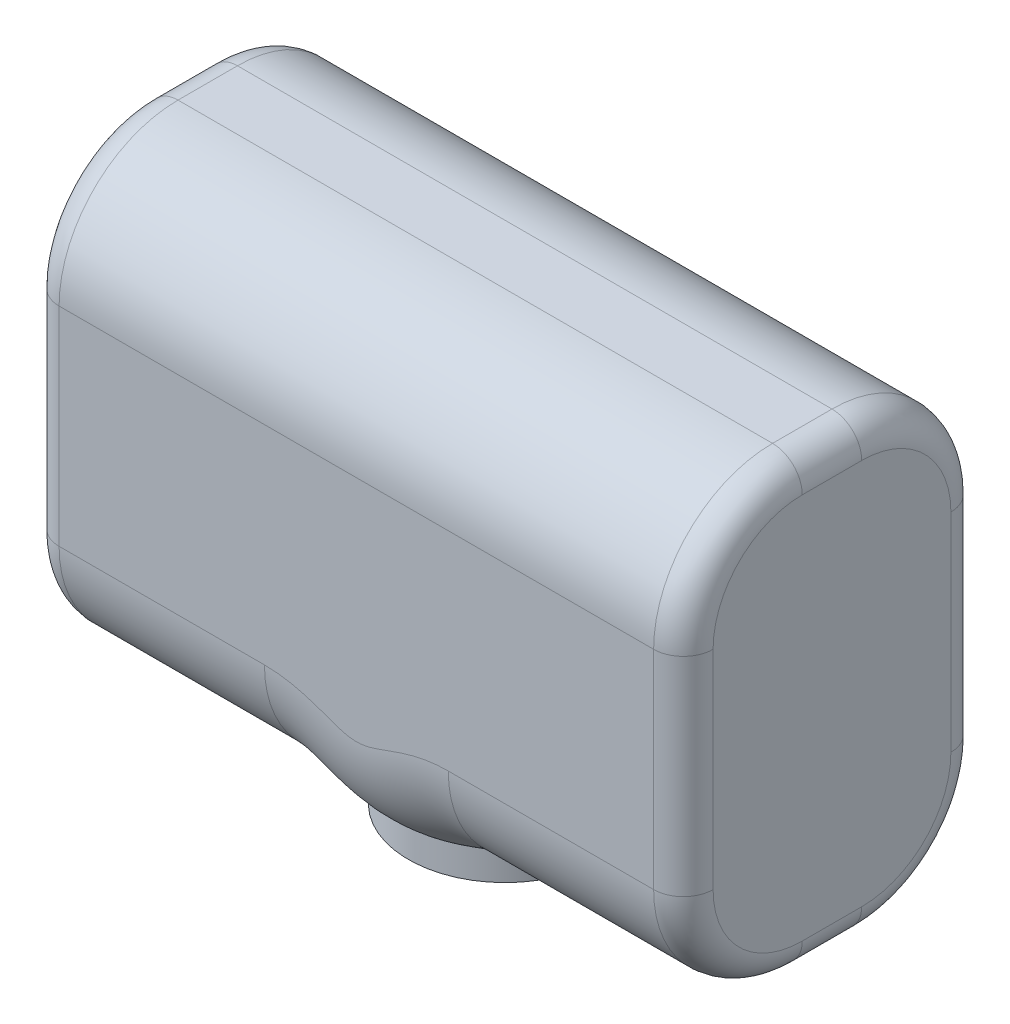
SolidWorks part; units mm, degrees
material "Custom Plastic"
ref_plane "Front Plane" through (0, 0, 0) normal (0, 0, 1) x (1, 0, 0)
ref_plane "Top Plane" through (0, 0, 0) normal (0, 1, 0) x (1, 0, 0)
ref_plane "Right Plane" through (0, 0, 0) normal (1, 0, 0) x (0, 0, -1)
sketch "Sketch1" plane through (0, 0, 0) normal (0, 1, 0) x (1, 0, 0)
  line L1 (-110, -50) -> (110, -50)
  line L2 (-110, -50) -> (-110, 50)
  line L3 (-110, 50) -> (110, 50)
  line L4 (110, -50) -> (110, 50)
  line L5 (-110, -50) -> (110, 50) construction
  line L6 (-110, 50) -> (110, -50) construction
  point P0 (0, 0)
  dimension "D1" = 220
  dimension "D2" = 100
extrude "Boss-Extrude1" add sketch "Sketch1" along normal blind 150
sketch "Sketch2" plane through (0, 0, 0) normal (0, -1, 0) x (1, 0, 0)
  circle A0 centre (0, 0) radius 32.5
  dimension "D1" = 65
extrude "Boss-Extrude2" add sketch "Sketch2" along normal blind 10
fillet "Fillet1" radius 40 4 edges at (0, 0, -50) (0, 0, 50) (0, 150, 50) (0, 150, -50)
fillet "Fillet2" radius 10 16 edges at (110, 11.7157, 38.2843) (110, 75, 50) (110, 138.2843, 38.2843) (110, 150, 0) (110, 138.2843, -38.2843) (110, 75, -50) (110, 11.7157, -38.2843) (110, 0, 0) (-110, 138.2843, -38.2843) (-110, 150, 0) (-110, 138.2843, 38.2843) (-110, 75, 50) (-110, 11.7157, 38.2843) (-110, 0, 0) (-110, 11.7157, -38.2843) (-110, 75, -50)
